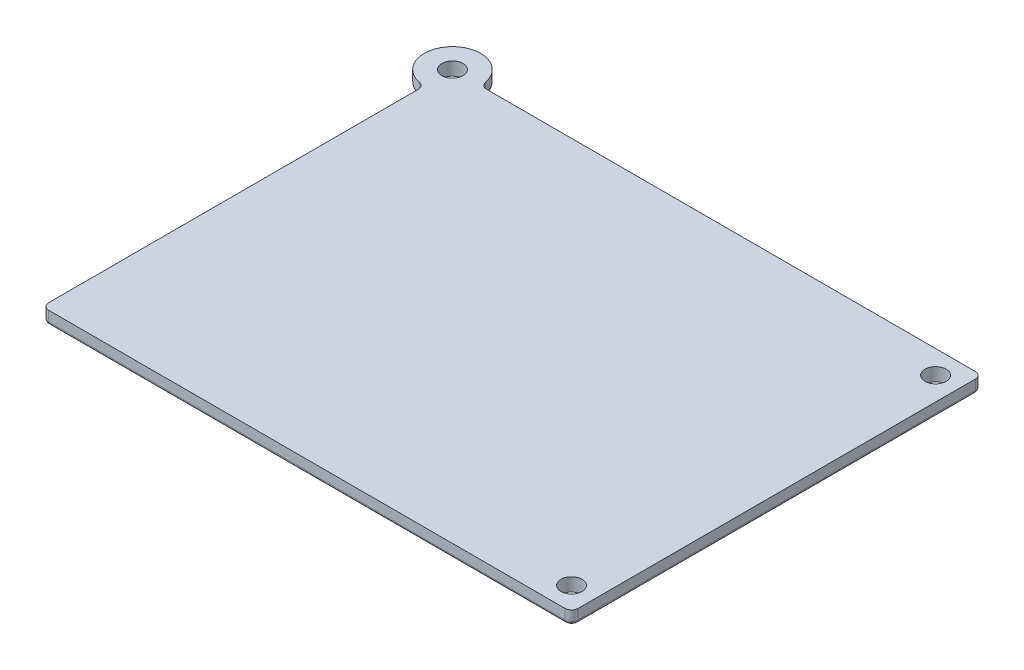
SolidWorks part; units mm, degrees
material "PVC Rigid"
ref_plane "Front Plane" through (0, 0, 0) normal (0, 0, 1) x (1, 0, 0)
ref_plane "Top Plane" through (0, 0, 0) normal (0, 1, 0) x (1, 0, 0)
ref_plane "Right Plane" through (0, 0, 0) normal (1, 0, 0) x (0, 0, -1)
sketch "Sketch1" plane through (0, 0, 0) normal (0, 1, 0) x (1, 0, 0)
  line L1 (-40, -31) -> (40, -31)
  line L2 (-40, -31) -> (-40, 25.8461)
  line L3 (-34.8461, 31) -> (40, 31)
  line L4 (40, -31) -> (40, 31)
  line L5 (-40, -31) -> (40, 31) construction
  line L6 (0, 0) -> (40, -31) construction
  arc A0 (-40, 25.8461) -> (-40.8095, 26.8278) centre (-41, 25.8461) ccw construction
  arc A1 (-35.8278, 31.8095) -> (-34.8461, 31) centre (-34.8461, 32) ccw construction
  arc A2 (-35.8278, 31.8095) -> (-40.8095, 26.8278) centre (-40, 31) ccw construction
  arc A3 (-40, 25.8461) -> (-40.8095, 26.8278) centre (-41, 25.8461) ccw
  arc A4 (-35.8278, 31.8095) -> (-34.8461, 31) centre (-34.8461, 32) ccw
  arc A5 (-35.8278, 31.8095) -> (-40.8095, 26.8278) centre (-40, 31) ccw
  point P0 (0, 0)
  dimension "D1" = 80
  dimension "D2" = 62
extrude "Main Body" add sketch "Sketch1" along normal blind 2
fillet "Corners" radius 1 3 edges at (-40, 1, 31) (40, 1, -31) (40, 1, 31)
fillet "Edge" radius 0.5 10 edges at (-39.7071, 0, 30.7071) (39.7071, 0, -30.7071) (39.7071, 0, 30.7071) (-40, 0, 2.0769) (2.0769, 0, -31) (40, 0, 0) (0, 0, 31) (-40.2285, 0, -26.4823) (-43.0052, 0, -34.0052) (-35.4823, 0, -31.2285)
sketch "Sketch7" plane through (0, 0, 0) normal (0, -1, 0) x (-1, 0, 0)
  circle A0 centre (-36.5, 27.5) radius 1.6
  circle A1 centre (-36.5, -27.5) radius 1.6
  circle A2 centre (-36.5, -27.5) radius 1.6 construction
  circle A3 centre (-36.5, 27.5) radius 1.6 construction
  circle A4 centre (40, 31) radius 1.6
  circle A5 centre (40, 31) radius 1.6 construction
extrude "Lid Holes" cut sketch "Sketch7" against normal through all both and the other way through all
sketch "Peg Angle" plane through (0, 0, 0) normal (0, -1, 0) x (-1, 0, 0)
  line L0 (39.5, -30) -> (19.4082, -13.9542) construction
  line L1 (-39.3536, -30.3536) -> (-19.8872, -10.8872) construction
  arc A0 (-39.5, -30) -> (-39, -30.5) centre (-39, -30) ccw construction
sketch "Sketch4" plane through (0, 0, 0) normal (0, -1, 0) x (-1, 0, 0)
  line L0 (-39.3536, -30.3536) -> (-19.8872, -10.8872) construction
  line L3 (-34.4038, -19.747) -> (-28.747, -25.4038) construction
  circle A0 centre (-34.4038, -19.747) radius 2.325
  circle A1 centre (-28.747, -25.4038) radius 2.325
  point P2 (-29.6048, -26.2617)
  point P8 (-31.5754, -22.5754)
  dimension "D1" = 4.65
  dimension "D3" = 4.65
  dimension "D2" = 4
  dimension "D4" = 8
  dimension "D5" = 11
extrude "Boss-Extrude3" add sketch "Sketch4" along normal blind 1.6
fillet "Fillet3" radius 0.05 2 edges at (34.4038, -1.6, 17.422) (28.747, -1.6, 23.0788)
pattern_linear "LPattern5" count 4 spacing 8 along (-0.7071, 0, -0.7071) of "Boss-Extrude3", "Fillet3"
sketch "Sketch9" plane through (0, 0, 0) normal (0, -1, 0) x (-1, 0, 0)
  line L0 (39.5, -30) -> (19.4082, -13.9542) construction
  line L2 (27.317, -25.3894) -> (32.3093, -19.1383) construction
  circle A0 centre (27.317, -25.3894) radius 2.325
  circle A1 centre (32.3093, -19.1383) radius 2.325
  arc A2 (39, -31) -> (40, -30) centre (39, -30) ccw construction
  point P0 (29.1604, -16.6235)
  point P8 (29.8131, -22.2639)
  point P11 (39.7071, -30.7071)
  dimension "D1" = 4.65
  dimension "D2" = 4.65
  dimension "D3" = 8
  dimension "D4" = 13
extrude "Pegs (Diagonal)" add sketch "Sketch9" along normal blind 1.6
fillet "Fillet6" radius 0.05 2 edges at (-27.317, -1.6, 23.0644) (-32.3093, -1.6, 16.8133)
pattern_linear "LPattern6" count 4 spacing 8 along (0.7814, 0, -0.624) of "Pegs (Diagonal)"
equation "\"D2@Sketch9\"=\"D1@Sketch9\""
equation "\"D3@Sketch4\"=\"D1@Sketch4\""
equation "\"D4@Sketch4\"=\"D2@Sketch4\"*2"
